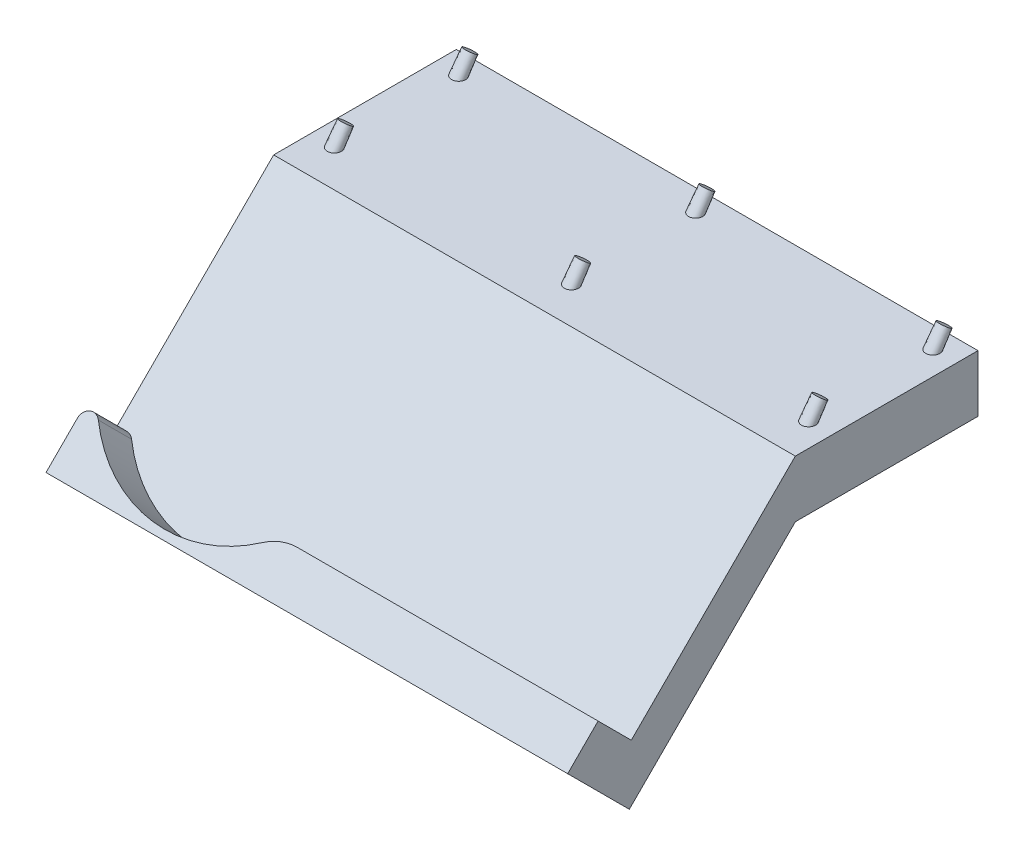
SolidWorks part; units mm, degrees
ref_plane "Front Plane" through (0, 0, 0) normal (0, 0, 1) x (1, 0, 0)
ref_plane "Top Plane" through (0, 0, 0) normal (0, 1, 0) x (1, 0, 0)
ref_plane "Right Plane" through (0, 0, 0) normal (1, 0, 0) x (0, 0, -1)
sketch "Sketch1" plane through (0, 0, 0) normal (0, 1, 0) x (1, 0, 0)
  line L1 (0, 28.5) -> (55, 28.5)
  line L2 (0, 28.5) -> (0, 0)
  line L3 (0, 0) -> (55, 0)
  line L4 (55, 28.5) -> (55, 0)
  dimension "D1" = 55
  dimension "D2" = 28.5
extrude "Boss-Extrude1" add sketch "Sketch1" along normal blind 50 contours L2 L3 L4 L1
sketch "Sketch4" plane through (55, 0, 0) normal (1, 0, 0) x (0, 0, -1)
  line L0 (28.5, 0) -> (0, 0) construction
  line L1 (-29.3553, 41.3553) -> (6, 76.7107)
  line L2 (-29.3553, 41.3553) -> (6, 6)
  line L3 (6, 6) -> (41.3553, 41.3553)
  line L4 (6, 76.7107) -> (41.3553, 41.3553)
  line L5 (0, 50) -> (0, 0) construction
  dimension "D1" = 50
  dimension "D2" = 50
  dimension "D3" = 6
  dimension "D4" = 6
extrude "Cut-Extrude1" cut sketch "Sketch4" against normal blind 50
sketch "Sketch5" plane through (55, 0, 0) normal (1, 0, 0) x (0, 0, -1)
  line L0 (0, 12) -> (0, 0) construction
  line L1 (-11.6421, 9.5) -> (-4.5711, 16.5711)
  line L2 (-11.6421, 9.5) -> (-4.5711, 2.4289)
  line L3 (-4.5711, 2.4289) -> (2.5, 9.5)
  line L4 (-4.5711, 16.5711) -> (2.5, 9.5)
  line L5 (0, 12) -> (6, 6) construction
  dimension "D1" = 10
  dimension "D2" = 10
  dimension "D3" = 2.5
extrude "Cut-Extrude2" cut sketch "Sketch5" against normal through all
sketch "Sketch12" plane through (55, 0, 0) normal (1, 0, 0) x (0, 0, -1)
  line L0 (2.5, 9.5) -> (6, 6)
  line L1 (6, 6) -> (6.7071, 6.7071)
  line L2 (6, 6) -> (28.5, 28.5) construction
  line L3 (6.7071, 6.7071) -> (3.2071, 10.2071)
  line L4 (3.2071, 10.2071) -> (2.5, 9.5)
  dimension "D1" = 1
extrude "Boss-Extrude2" add sketch "Sketch12" against normal through all contours L3 L4 L0 L1
sketch "Sketch6" plane through (0, 0, 0) normal (0, 0.7071, 0.7071) x (1, 0, 0)
  line L0 (55, 4.9497) -> (0, 4.9497) construction
  line L3 (0, 55.5079) -> (0, 35.3553) construction
  circle A0 centre (12, 19.4497) radius 13.75
  dimension "D1" = 27.5
  dimension "D2" = 14.5
  dimension "D3" = 12
extrude "Cut-Extrude3" cut sketch "Sketch6" along normal through all
ref_axis "Axis2" through (12, 34.8672, 7.3611) along (0, -0.7071, -0.7071)
sketch "Sketch7" plane through (55, 0, 0) normal (1, 0, 0) x (0, 0, -1)
  line L0 (0, 7) -> (5.5063, 12.5063)
  line L1 (18.4998, 18.4998) -> (9.0063, 9.0063) construction
  line L2 (5.5063, 12.5063) -> (9.0063, 9.0063)
  line L3 (9.0063, 9.0063) -> (57, 57)
  line L4 (57, 57) -> (25.4084, 57)
  line L5 (25.4084, 57) -> (0, 57)
  line L6 (0, 57) -> (0, 7)
  line L7 (9.0063, 9.0063) -> (0, 18.0127) construction
  line L8 (6.7071, 6.7071) -> (28.5, 28.5) construction
  dimension "D1" = 50
extrude "Cut-Extrude4" cut sketch "Sketch7" against normal through all contours L5 L6 L0 L2 L3 L4
sketch "Sketch8" plane through (0, 0, 0) normal (0, 1, 0) x (1, 0, 0)
  line L0 (12, -7.3611) -> (12, 9.0686) construction
  line L3 (55, 28.5) -> (0, 28.5) construction
  circle A0 centre (25.75, 30) radius 6
  dimension "D1" = 12
  dimension "D3" = 1.5
  dimension "D2" = 13.75
extrude "Cut-Extrude5" cut sketch "Sketch8" along normal through all contours A0
pattern_linear "LPattern1" count 2 spacing 27.5 along (-1, 0, 0) of "Cut-Extrude5"
sketch "Sketch9" plane through (55, 0, 0) normal (1, 0, 0) x (0, 0, -1)
  line L0 (24, 24) -> (28.5, 24)
  line L1 (28.5, 28.5) -> (28.5, 0) construction
  line L2 (28.5, 24) -> (28.5, 28.5)
  line L3 (28.5, 28.5) -> (24, 24)
extrude "Cut-Extrude6" cut sketch "Sketch9" against normal through all
sketch "Sketch10" plane through (0, 0, 0) normal (0, 1, 0) x (1, 0, 0)
  line L0 (0, 24) -> (25.75, 24) construction
  line L1 (55, 24) -> (0, 24)
  line L2 (55, 24) -> (55, 28.5)
  line L3 (55, 28.5) -> (0, 28.5)
  line L4 (0, 24) -> (0, 28.5)
  line L5 (0, 24) -> (0, 9.0063) construction
extrude "Cut-Extrude7" cut sketch "Sketch10" along normal through all
fillet "Fillet5" radius 1 1 edges at (0, 10.7563, -7.2563) tangent propagation no
fillet "Fillet6" radius 5 1 edges at (21.4748, 8.4571, -4.9571)
sketch "Sketch16" plane through (55, 0, 0) normal (1, 0, 0) x (0, 0, -1)
  line L0 (24, 18) -> (6.5, 0.5)
  line L1 (24, 24) -> (24, 0) construction
  line L2 (6.5, 0.5) -> (0, 7)
  line L3 (0, 7) -> (0, 0)
  line L4 (0, 0) -> (24, 0)
  line L5 (24, 0) -> (24, 18)
  line L6 (6.7071, 6.7071) -> (24, 24) construction
  dimension "D1" = 6
extrude "Cut-Extrude8" cut sketch "Sketch16" against normal through all
sketch "Sketch17" plane through (0, 0, -24) normal (0, 0, -1) x (-1, 0, 0)
  line L1 (-55, 24) -> (0, 24)
  line L2 (-55, 24) -> (-55, 18)
  line L3 (-55, 18) -> (0, 18)
  line L4 (0, 24) -> (0, 18)
  dimension "D1" = 6
extrude "Boss-Extrude4" add sketch "Sketch17" along normal blind 19.26
sketch "Bottom" plane through (0, 24, 0) normal (0, 1, 0) x (1, 0, 0)
  line L0 (0, 24) -> (55, 24) construction
  circle A0 centre (2.5, 27.9) radius 0.75
  point P6 (27.5, 24)
  dimension "D1" = 1.5
  dimension "D3" = 3.9
  dimension "D2" = 25
ref_plane "Plane1" through (0, 26, 0) normal (0, 1, 0) x (1, 0, 0)
sketch "Top" plane through (0, 26, 0) normal (0, 1, 0) x (1, 0, 0)
  line L0 (0, 24) -> (55, 24) construction
  circle A0 centre (2.5, 29.3) radius 0.7
  point P4 (27.5, 24)
  dimension "D1" = 1.4
  dimension "D3" = 25
  dimension "D4" = 1.4
loft "Loft1" add profiles "Bottom", "Top" connector at (2.5, 24, -27.15) connector at (2.5, 26, -28.6)
sketch "Sketch24" plane through (0, 0, 0) normal (1, 0, 0) x (0, 0, -1)
  line L0 (28.6, 26) -> (30, 26)
  line L1 (30, 26) -> (29.5618, 25.3508)
  line L2 (28.65, 24) -> (30, 26) construction
  line L3 (29.5618, 25.3508) -> (28.6, 26)
extrude "Cut-Extrude9" cut sketch "Sketch24" along normal through all
pattern_linear "LPattern3" count 3 spacing 25 along (1, 0, 0) count 2 spacing 13.1 along (0, 0, -1) of "Loft1", "Cut-Extrude9"
sketch "Sketch29" plane through (0, 18, 0) normal (0, -1, 0) x (1, 0, 0)
  line L0 (22.5, -33.26) -> (22.5, -43.26)
  line L1 (55, -43.26) -> (0, -43.26) construction
  line L2 (22.5, -43.26) -> (24.5, -43.26)
  line L3 (24.5, -43.26) -> (24.5, -33.26)
  line L4 (30.5, -33.26) -> (30.5, -43.26)
  line L5 (30.5, -43.26) -> (32.5, -43.26)
  line L6 (32.5, -43.26) -> (32.5, -33.26)
  arc A0 (22.5, -33.26) -> (32.5, -33.26) centre (27.5, -33.26) cw
  arc A1 (24.5, -33.26) -> (30.5, -33.26) centre (27.5, -33.26) cw
  point P6 (27.5, -43.26)
  point P14 (27.5, -43.26)
  dimension "D3" = 10
  dimension "D4" = 3
  dimension "D1" = 2
  dimension "D2" = 2
extrude "Cut-Extrude10" cut sketch "Sketch29" against normal blind 4 contours A0 L6 L5 L4 A1 L3 L2 L0
